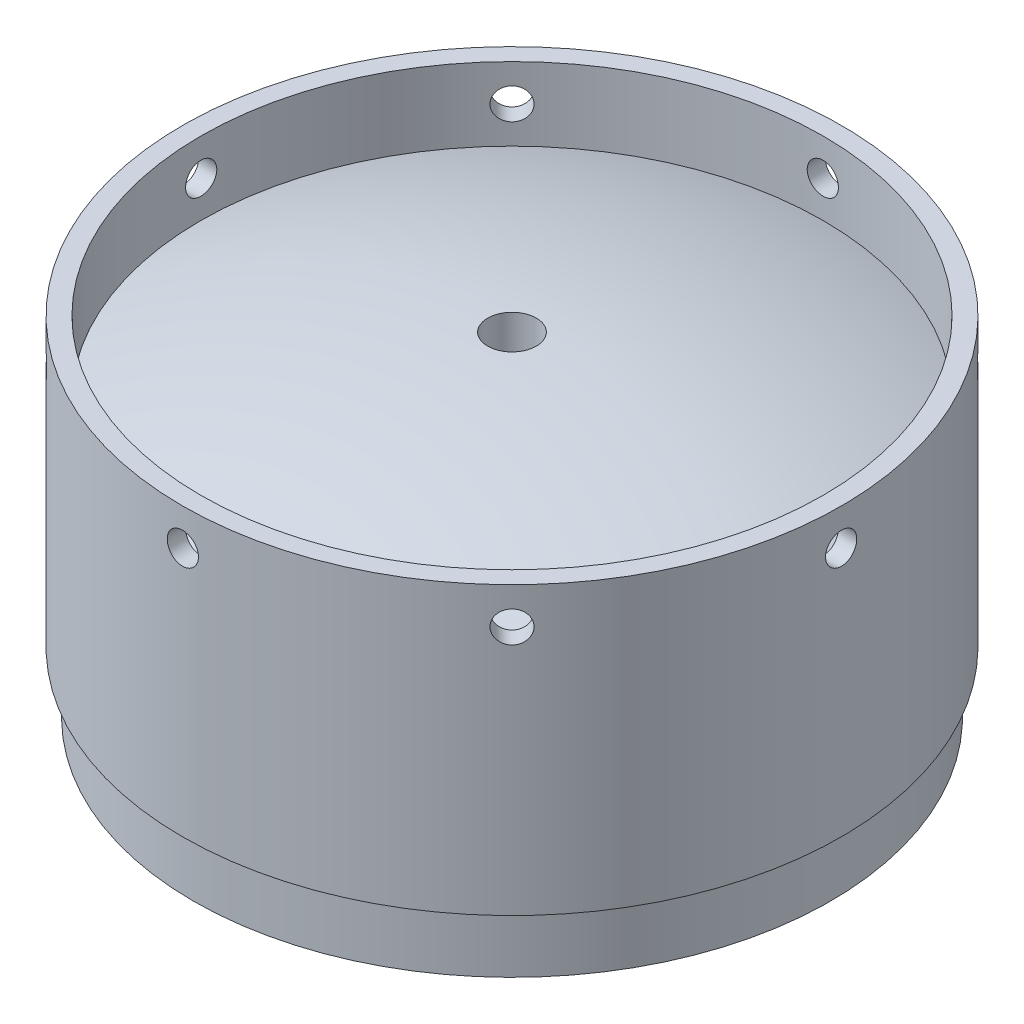
SolidWorks part; units mm, degrees
material "6061-T6 (SS)"
ref_plane "Front Plane" through (0, 0, 0) normal (0, 0, 1) x (1, 0, 0)
ref_plane "Top Plane" through (0, 0, 0) normal (0, 1, 0) x (1, 0, 0)
ref_plane "Right Plane" through (0, 0, 0) normal (1, 0, 0) x (0, 0, -1)
ref_axis "Axis1" through (0, 127.061, 0) along (0, -1, 0)
sketch "Sketch1" plane through (0, 0, 0) normal (0, 0, 1) x (1, 0, 0)
  line L0 (-57.15, 10.6249) -> (-57.15, 60.325)
  line L1 (-55.245, 9.525) -> (-57.15, 10.6249)
  line L2 (0, 127.061) -> (0, -81.9141) construction
  line L4 (-55.245, 9.525) -> (-55.245, 0)
  line L5 (-55.245, 0) -> (-53.975, 0)
  line L6 (55, 0) -> (-55, 0) construction
  line L7 (-53.975, 60.325) -> (-57.15, 60.325)
  line L8 (-57.15, 10.6249) -> (-55.245, 9.525)
  line L10 (-4.2164, 57.8559) -> (-4.2164, 50.8678)
  line L11 (-53.975, 47.625) -> (-53.975, 60.325)
  line L15 (-53.975, 0) -> (-53.975, 9.525)
  line L16 (-53.975, 9.525) -> (-50.7819, 27.6338)
  arc A0 (-50.7819, 27.6338) -> (-36.7422, 46.0132) centre (-31.7319, 27.6338) cw
  arc A1 (-36.7422, 46.0132) -> (-4.2164, 50.8678) centre (0, -88.7685) cw
  arc A3 (-53.975, 47.625) -> (-4.2164, 57.8559) centre (0, -88.7685) cw
  point P14 (-54.61, 0)
  dimension "D5" = 19.05
  dimension "D6" = 139.7
  dimension "D7" = 146.685
  dimension "D8" = 50.8
  dimension "D2" = 170
  dimension "D3" = 9.525
  dimension "D4" = 1.27
  dimension "D9" = 12.7
  dimension "D10" = 3.175
  dimension "D13" = 4.2164
  dimension "D15" = 3.175
  dimension "D16" = 57.15
  dimension "D17" = 120
revolve "Revolve2" add sketch "Sketch1" angle 360 about axis through (0, 127.061, 0) along (0, -1, 0) region at (-56.3474, 35.4749, 0)
sketch "Sketch2" plane through (0, 0, 0) normal (0, 0, 1) x (1, 0, 0)
  line L0 (0, 127.061) -> (0, -81.9141) construction
  line L1 (0, 87.1374) -> (-97.8719, 87.1374)
  line L2 (0, 87.1374) -> (0, -26.2798)
  line L3 (0, -26.2798) -> (-97.8719, -26.2798)
  line L4 (-97.8719, 87.1374) -> (-97.8719, -26.2798)
revolve "Cut-Revolve1" [suppressed] cut sketch "Sketch2" angle 315 about axis through (0, 127.061, 0) along (0, -1, 0)
ref_plane "Plane1" through (0, 53.975, 0) normal (0, 1, 0) x (1, 0, 0)
ref_axis "Axis2" through (0, 53.975, -62.865) along (0, 0, 1)
hole_wizard "#3 (0.213) Diameter Hole1" positions "3DSketch3" profile "Sketch5" hole size "#3" standard "ANSI Inch"
sketch3d "3DSketch3"
  line L0 (0, 53.975, -62.865) -> (0, 53.975, 62.865) construction
  point P0 (0, 53.975, 57.15)
sketch "Sketch5" plane through (0, 53.975, 57.15) normal (1, 0, 0) x (0, -1, 0)
  line L0 (0, 0) -> (0, 13.3094)
  line L1 (0, 13.3094) -> (2.7051, 11.684)
  line L2 (2.7051, 11.684) -> (2.7051, 0)
  line L5 (2.7051, 0) -> (0, 0)
  line L10 (0, 13.3094) -> (-2.7051, 11.684) construction
  line L11 (0, -6.35) -> (0, 107.95) construction
  dimension "Hole Dia." = 5.4102
  dimension "Hole Depth" = 11.684
  dimension "Drill Angle" = 118
pattern_circular "CirPattern1" count 8 over 360 about axis through (0, 127.061, 0) along (0, -1, 0) of "#3 (0.213) Diameter Hole1"
cosmetic thread "Cosmetic Thread1" parameters "D2"=6.35
ref_plane "Plane2" through (0, 9.525, 0) normal (0, -1, 0) x (-1, 0, 0)
sketch "Sketch7" plane through (0, 9.525, 0) normal (0, -1, 0) x (-1, 0, 0)
  circle A0 centre (0, 0) radius 56.515
  dimension "D1" = 113.03
extrude "Boss-Extrude2" [suppressed] add sketch "Sketch7" against normal blind 41.91 separate body
combine bodies "Combine2" [suppressed] operation type subtract main body 113 bodies to subtract 110
sketch "Sketch8" plane through (0, 0, 0) normal (0, 0, 1) x (1, 0, 0)
  line L0 (0, 127.061) -> (0, -81.9141) construction
  line L1 (0, 89.8009) -> (92.4947, 89.8009)
  line L2 (0, 89.8009) -> (0, -18.1338)
  line L3 (0, -18.1338) -> (92.4947, -18.1338)
  line L4 (92.4947, 89.8009) -> (92.4947, -18.1338)
revolve "Cut-Revolve2" [suppressed] cut sketch "Sketch8" angle 300 about axis through (0, 127.061, 0) along (0, -1, 0) other way angle 30 reverse direction yes
